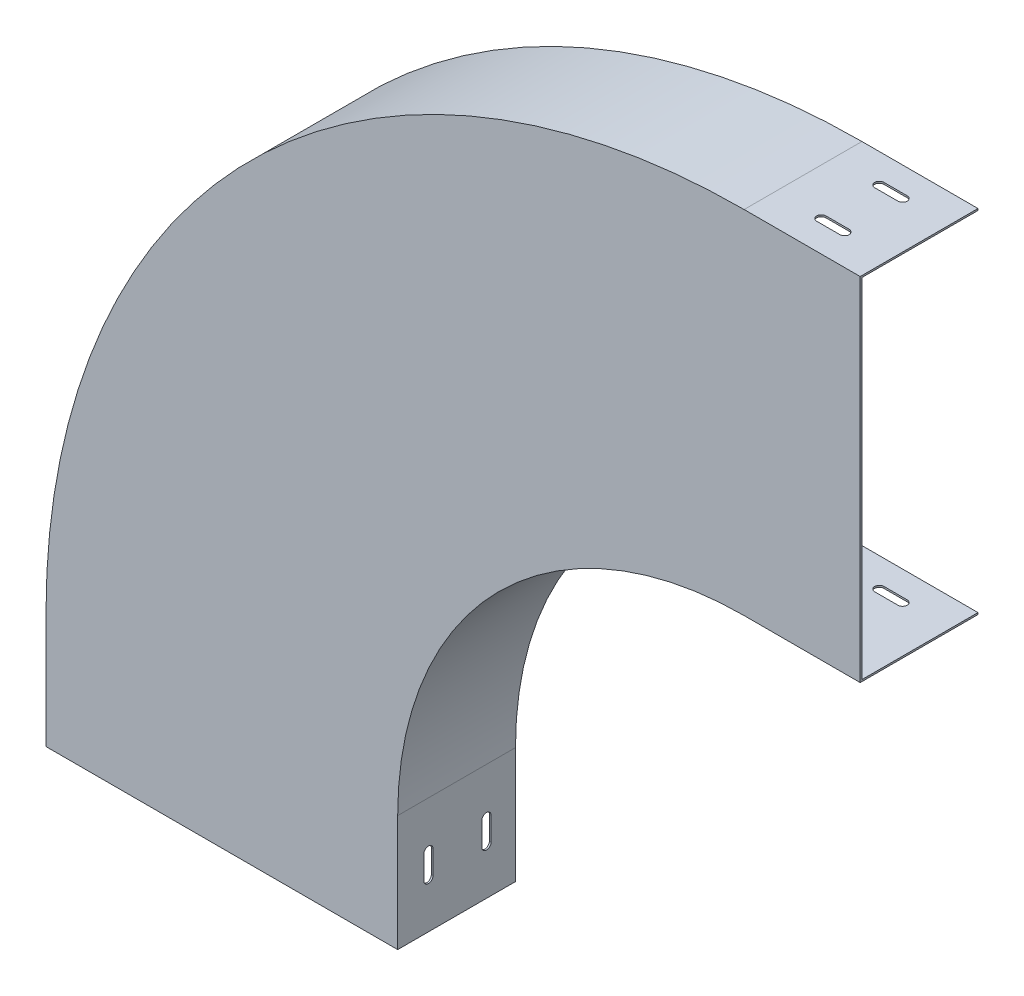
SolidWorks part; units mm, degrees
ref_plane "Front Plane" through (0, 0, 0) normal (0, 0, 1) x (1, 0, 0)
ref_plane "Top Plane" through (0, 0, 0) normal (0, 1, 0) x (1, 0, 0)
ref_plane "Right Plane" through (0, 0, 0) normal (1, 0, 0) x (0, 0, -1)
sketch "ElbowArc" plane through (0, 0, 0) normal (0, 0, 1) x (1, 0, 0)
  line L0 (450, 0) -> (550, 0)
  line L1 (0, -450) -> (0, -550)
  arc A0 (0, -450) -> (450, 0) centre (450, -450) cw
  dimension "BendRadius" = 450
  dimension "ArmLength" = 100
  dimension "BendAngle" = 90
ref_plane "RoutePlane" through (0, -550, 0) normal (0, -1, 0) x (-1, 0, 0)
sketch "Sketch1" plane through (0, -550, 0) normal (0, 1, 0) x (1, 0, 0)
  line L0 (0, 0) -> (203.1914, 0) construction
  line L1 (150, 0) -> (-150, 0)
  line L2 (-150, 0) -> (-150, 100)
  line L3 (150, 0) -> (150, 100)
  line L4 (-151.5, -1.5) -> (-151.5, 100)
  line L5 (151.5, -1.5) -> (-151.5, -1.5)
  line L6 (151.5, -1.5) -> (151.5, 100)
  line L7 (151.5, 100) -> (150, 100)
  line L8 (-150, 100) -> (-151.5, 100)
  dimension "Width" = 300
  dimension "AlignmentAngle" = 0
  dimension "Height" = 100
  dimension "Thickness" = 1.5
sweep "Sweep1" add profiles "Sketch1" path "ElbowArc"
ref_plane "Plane1" through (0, 0, 0) normal (1, 0, 0) x (0, -1, 0)
sketch "Sketch2" plane through (0, 0, 0) normal (1, 0, 0) x (0, 0, -1)
  line L0 (0, -500) -> (50, -500) construction
  line L1 (0, -450) -> (0, -550) construction
  line L2 (50, -500) -> (100, -500) construction
  line L3 (50, -550) -> (50, -450) construction
  line L7 (25, -510) -> (25, -490) construction
  line L8 (21, -510) -> (21, -490)
  line L9 (29, -510) -> (29, -490)
  line L10 (75, -510) -> (75, -490) construction
  line L11 (71, -510) -> (71, -490)
  line L12 (79, -510) -> (79, -490)
  arc A0 (21, -510) -> (29, -510) centre (25, -510) ccw
  arc A1 (29, -490) -> (21, -490) centre (25, -490) ccw
  arc A2 (71, -510) -> (79, -510) centre (75, -510) ccw
  arc A3 (79, -490) -> (71, -490) centre (75, -490) ccw
  point P10 (25, -500)
  point P16 (75, -500)
  dimension "D1" = 4
  dimension "D2" = 20
  dimension "D3" = 100
  dimension "D5" = 50
extrude "Cut-Extrude1" cut sketch "Sketch2" against normal through all and the other way through all
ref_plane "Plane2" through (0, 0, 0) normal (0, 1, 0) x (1, 0, 0)
sketch "Sketch3" plane through (0, 0, 0) normal (0, -1, 0) x (-1, 0, 0)
  line L0 (-500, 50) -> (-500, 0) construction
  line L1 (-550, 100) -> (-550, -1.5) construction
  line L2 (-450, 0) -> (-550, 0) construction
  line L4 (-500, 50) -> (-500, 100) construction
  line L6 (-450, 50) -> (-550, 50) construction
  line L9 (-510, 75) -> (-490, 75) construction
  line L10 (-510, 79) -> (-490, 79)
  line L11 (-510, 71) -> (-490, 71)
  line L12 (-510, 25) -> (-490, 25) construction
  line L13 (-510, 29) -> (-490, 29)
  line L14 (-510, 21) -> (-490, 21)
  arc A0 (-510, 79) -> (-510, 71) centre (-510, 75) ccw
  arc A1 (-490, 71) -> (-490, 79) centre (-490, 75) ccw
  arc A2 (-510, 29) -> (-510, 21) centre (-510, 25) ccw
  arc A3 (-490, 21) -> (-490, 29) centre (-490, 25) ccw
  point P12 (-500, 75)
  point P18 (-500, 25)
  dimension "D1" = 4
  dimension "D2" = 20
  dimension "D3" = 100
  dimension "D5" = 50
extrude "Cut-Extrude2" cut sketch "Sketch3" against normal through all and the other way through all
sketch "Sketch4" plane through (0, 0, 0) normal (0, 0, -1) x (-1, 0, 0)
  point P0 (0, -550)
  point P1 (-550, 0)
other "CPoint1" parameters "Diameter"=10, "StubLength"=300
ref_axis "Axis2" through (560, 0, 0) along (-1, 0, 0)
other "CPoint2" parameters "Diameter"=10, "StubLength"=300
ref_axis "Axis3" through (0, -560, 0) along (0, 1, 0)
equation "\"D1\"= \"AlignmentAngle@Sketch1\""
equation "\"D5@Sketch3\"=\"Height@Sketch1\"/2"
equation "\"D5@Sketch2\"=\"Height@Sketch1\"/2"
equation "\"D1@Plane1\"=\"AlignmentAngle@Sketch1\""
equation "\"D1@Plane2\"=\"AlignmentAngle@Sketch1\""
